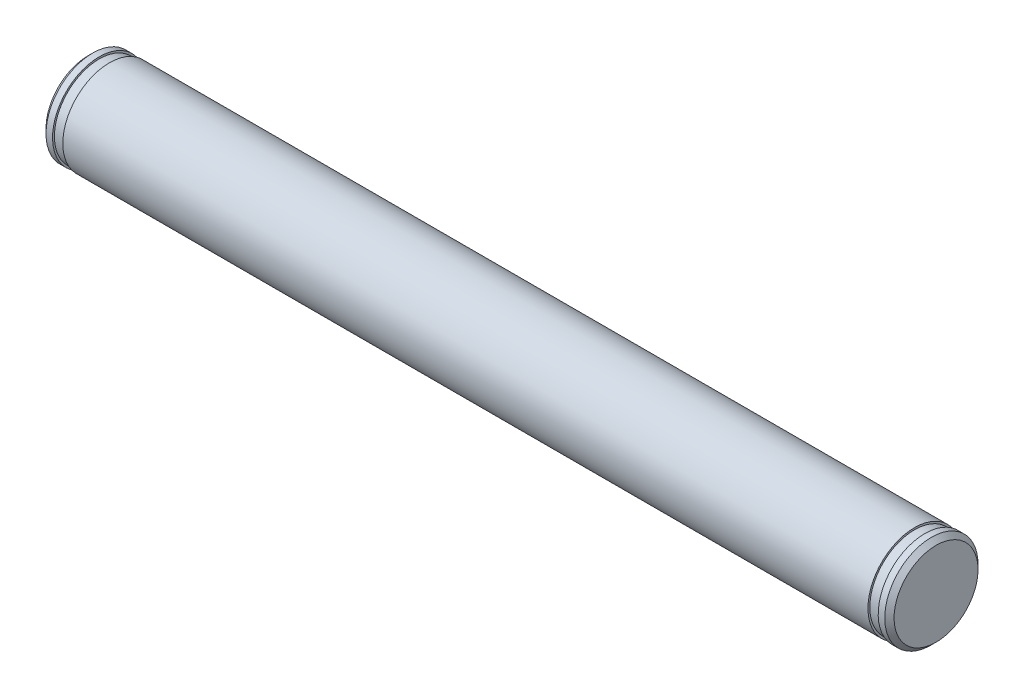
SolidWorks part; units mm, degrees
note: '?' marks a value the reader was unsure of.
ref_plane "前视基准面" through (0, 0, 0) normal (0, 0, 1) x (1, 0, 0)
ref_plane "上视基准面" through (0, 0, 0) normal (0, 1, 0) x (1, 0, 0)
ref_plane "右视基准面" through (0, 0, 0) normal (1, 0, 0) x (0, 0, -1)
other "Configuration Table"
sketch "草图1" plane through (0, 0, 0) normal (0, 0, 1) x (1, 0, 0)
  line L0 (-45.45, 0) -> (45.45, 0) construction
  line L1 (45.45, 0) -> (45.45, 5)
  line L2 (45.45, 5) -> (44.25, 5)
  line L3 (44.25, 5) -> (44.25, 4.8)
  line L4 (44.25, 4.8) -> (43.15, 4.8)
  line L5 (43.15, 4.8) -> (43.15, 5)
  line L6 (43.15, 5) -> (-43.15, 5)
  line L7 (0, 5) -> (0, 0) construction
  line L8 (43.25, 4.8) -> (43.25, 0) construction
  line L9 (-45.45, 0) -> (-45.45, 5)
  line L10 (-43.25, 4.8) -> (-43.25, 0) construction
  line L11 (-43.15, 4.8) -> (-43.15, 5)
  line L12 (-44.25, 4.8) -> (-43.15, 4.8)
  line L13 (-44.25, 5) -> (-44.25, 4.8)
  line L14 (-45.45, 5) -> (-44.25, 5)
  line L15 (45.45, 0) -> (-45.45, 0)
  dimension "D1" = 1.1
  dimension "D2" = 1
  dimension "D3" = 10
  dimension "D4" = 9.6
  dimension "D5" = 1.2
  dimension "D6" = 86.5
revolve "旋转1" add sketch "草图1" angle 360 about L15
chamfer "倒角1" distance 0.5 angle 45 2 edges at (45.45, 5, 0) (-45.45, 5, 0)
ref_plane "基准面1" through (43.25, 0, 0) normal (1, 0, 0) x (0, 0, -1)
ref_axis "基准轴1" through (-43.15, 0, 0) along (1, 0, 0)?
